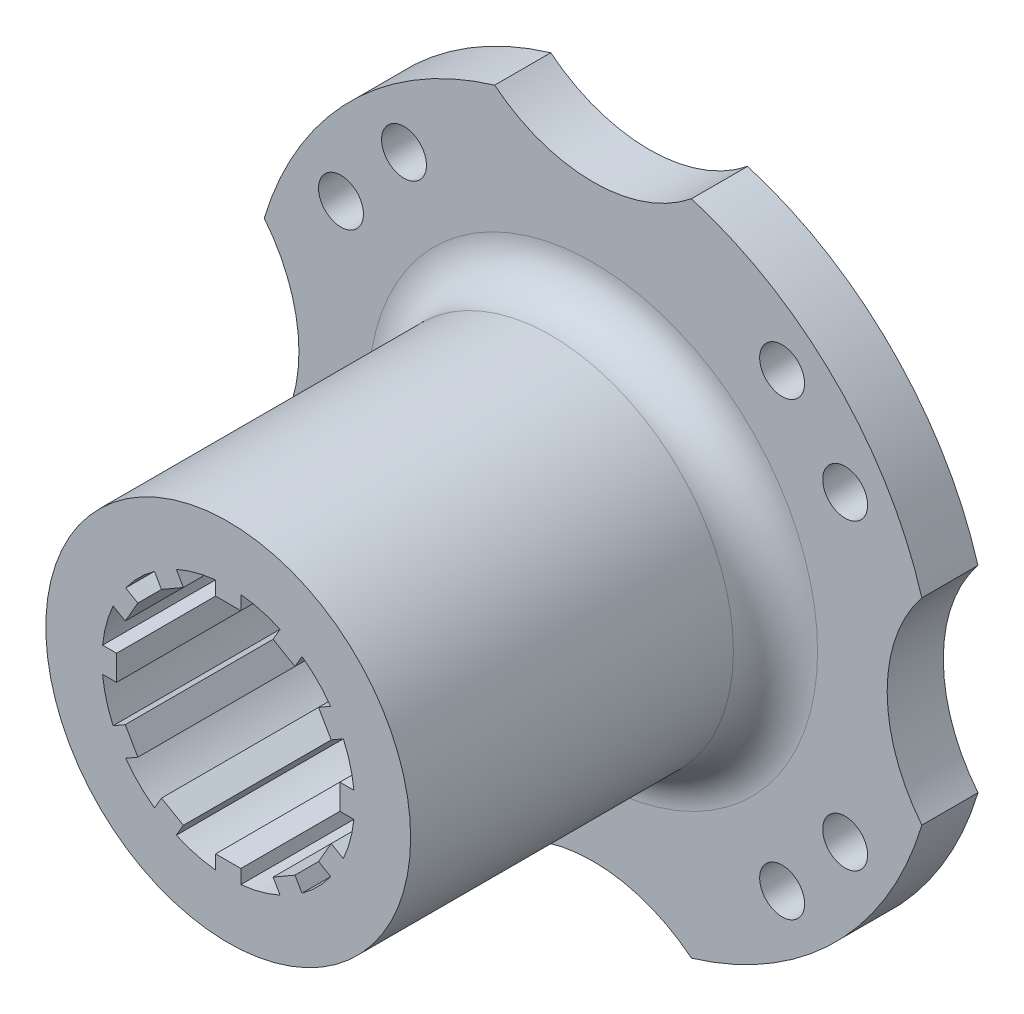
SolidWorks part; units mm, degrees
ref_plane "Front Plane" through (0, 0, 0) normal (0, 0, 1) x (1, 0, 0)
ref_plane "Top Plane" through (0, 0, 0) normal (0, 1, 0) x (1, 0, 0)
ref_plane "Right Plane" through (0, 0, 0) normal (1, 0, 0) x (0, 0, -1)
sketch "Sketch1" plane through (0, 0, 0) normal (0, 0, 1) x (1, 0, 0)
  line L0 (82.5, 0) -> (-82.5, 0) construction
  line L1 (0, -82.5) -> (0, 82.5) construction
  line L2 (-4.5, 44.7744) -> (-4.5, 39.7744)
  line L3 (-4.5, 39.7744) -> (4.5, 39.7744)
  line L4 (4.5, 39.7744) -> (4.5, 44.7744)
  line L5 (15.9901, 36.6957) -> (23.7843, 32.1957)
  line L6 (18.4901, 41.0258) -> (15.9901, 36.6957)
  line L7 (23.7843, 32.1957) -> (26.2843, 36.5258)
  line L8 (32.1957, 23.7843) -> (36.6957, 15.9901)
  line L9 (36.5258, 26.2843) -> (32.1957, 23.7843)
  line L10 (36.6957, 15.9901) -> (41.0258, 18.4901)
  line L11 (39.7744, 4.5) -> (39.7744, -4.5)
  line L12 (44.7744, 4.5) -> (39.7744, 4.5)
  line L13 (39.7744, -4.5) -> (44.7744, -4.5)
  line L14 (36.6957, -15.9901) -> (32.1957, -23.7843)
  line L15 (41.0258, -18.4901) -> (36.6957, -15.9901)
  line L16 (32.1957, -23.7843) -> (36.5258, -26.2843)
  line L17 (23.7843, -32.1957) -> (15.9901, -36.6957)
  line L18 (26.2843, -36.5258) -> (23.7843, -32.1957)
  line L19 (15.9901, -36.6957) -> (18.4901, -41.0258)
  line L20 (4.5, -39.7744) -> (-4.5, -39.7744)
  line L21 (4.5, -44.7744) -> (4.5, -39.7744)
  line L22 (-4.5, -39.7744) -> (-4.5, -44.7744)
  line L23 (-15.9901, -36.6957) -> (-23.7843, -32.1957)
  line L24 (-18.4901, -41.0258) -> (-15.9901, -36.6957)
  line L25 (-23.7843, -32.1957) -> (-26.2843, -36.5258)
  line L26 (-32.1957, -23.7843) -> (-36.6957, -15.9901)
  line L27 (-36.5258, -26.2843) -> (-32.1957, -23.7843)
  line L28 (-36.6957, -15.9901) -> (-41.0258, -18.4901)
  line L29 (-39.7744, -4.5) -> (-39.7744, 4.5)
  line L30 (-44.7744, -4.5) -> (-39.7744, -4.5)
  line L31 (-39.7744, 4.5) -> (-44.7744, 4.5)
  line L32 (-36.6957, 15.9901) -> (-32.1957, 23.7843)
  line L33 (-41.0258, 18.4901) -> (-36.6957, 15.9901)
  line L34 (-32.1957, 23.7843) -> (-36.5258, 26.2843)
  line L35 (-23.7843, 32.1957) -> (-15.9901, 36.6957)
  line L36 (-26.2843, 36.5258) -> (-23.7843, 32.1957)
  line L37 (-15.9901, 36.6957) -> (-18.4901, 41.0258)
  circle A0 centre (0, 0) radius 122.3
  circle A1 centre (0, 0) radius 104.8 construction
  circle A2 centre (67.3641, 80.2815) radius 8
  circle A3 centre (89.8311, 53.976) radius 8
  circle A4 centre (67.3641, -80.2815) radius 8
  circle A5 centre (89.8311, -53.976) radius 8
  circle A6 centre (-67.3641, 80.2815) radius 8
  circle A7 centre (-89.8311, 53.976) radius 8
  circle A8 centre (-89.8311, -53.976) radius 8
  circle A9 centre (-67.3641, -80.2815) radius 8
  arc A10 (-44.7744, -4.5) -> (-41.0258, -18.4901) centre (0, 0) ccw
  circle A11 centre (0, 0) radius 65
  arc A12 (117.1655, -35.0647) -> (117.1655, 35.0647) centre (160.6992, 0) cw
  arc A13 (-35.0647, -117.1655) -> (35.0647, -117.1655) centre (0, -160.6992) cw
  arc A14 (-117.1655, 35.0647) -> (-117.1655, -35.0647) centre (-160.6992, 0) cw
  arc A15 (35.0647, 117.1655) -> (-35.0647, 117.1655) centre (0, 160.6992) cw
  circle A16 centre (0, 0) radius 45 construction
  arc A17 (-41.0258, 18.4901) -> (-44.7744, 4.5) centre (0, 0) ccw
  arc A18 (-26.2843, 36.5258) -> (-36.5258, 26.2843) centre (0, 0) ccw
  arc A19 (-4.5, 44.7744) -> (-18.4901, 41.0258) centre (0, 0) ccw
  arc A20 (18.4901, 41.0258) -> (4.5, 44.7744) centre (0, 0) ccw
  arc A21 (36.5258, 26.2843) -> (26.2843, 36.5258) centre (0, 0) ccw
  arc A22 (44.7744, 4.5) -> (41.0258, 18.4901) centre (0, 0) ccw
  arc A23 (41.0258, -18.4901) -> (44.7744, -4.5) centre (0, 0) ccw
  arc A24 (26.2843, -36.5258) -> (36.5258, -26.2843) centre (0, 0) ccw
  arc A25 (4.5, -44.7744) -> (18.4901, -41.0258) centre (0, 0) ccw
  arc A26 (-18.4901, -41.0258) -> (-4.5, -44.7744) centre (0, 0) ccw
  arc A27 (-36.5258, -26.2843) -> (-26.2843, -36.5258) centre (0, 0) ccw
  point P30 (104.8, 0)
  point P43 (0, 0)
  point P44 (0, 39.7744)
  point P93 (0, 0)
  dimension "D1" = 244.6
  dimension "D2" = 16
  dimension "D3" = 16
  dimension "D5" = 209.6
  dimension "D6" = 20
  dimension "D7" = 90
  dimension "D9" = 4
  dimension "D4" = 19
  dimension "D8" = 62
  dimension "D10" = 9
  dimension "D11" = 5
  dimension "D12" = 12
extrude "Boss-Extrude1" add sketch "Sketch1" along normal blind 20 contours A0 A15 A14 A13 A12 A11 A9 A8 A6 A4 A3 A2 A5 A7 | A11 A10 region at (101.4861, 0, 0) region at (-63.1615, 0, 0)
extrude "Boss-Extrude2" add sketch "Sketch1<3>" along normal blind 130 from surface contours A11 A10 region at (-63.1615, 0, 0) starting at face at (-59.3641, -80.2815, 20)
sketch "Sketch1<3>" plane through (0, 0, 0) normal (0, 0, 1) x (1, 0, 0) same geometry as "Sketch1"
sketch "Sketch2" plane through (0, 0, 0) normal (0, 0, -1) x (-1, 0, 0)
  circle A0 centre (0, 0) radius 55
  circle A1 centre (0, 0) radius 30
  dimension "D1" = 110
extrude "Cut-Extrude1" cut sketch "Sketch2" against normal blind 20
extrude "Boss-Extrude3" add sketch "Sketch2<2>" against normal blind 10 from surface starting at face at (0, 0, 20)
sketch "Sketch2<2>" plane through (0, 0, 0) normal (0, 0, -1) x (-1, 0, 0) same geometry as "Sketch2"
fillet "Fillet1" radius 15 1 edges at (65, 0, 20)
fillet "Fillet2" radius 4 2 edges at (-30, 0, 20) (-30, 0, 30)
fillet "Fillet3" radius 5 1 edges at (-55, 0, 20)
